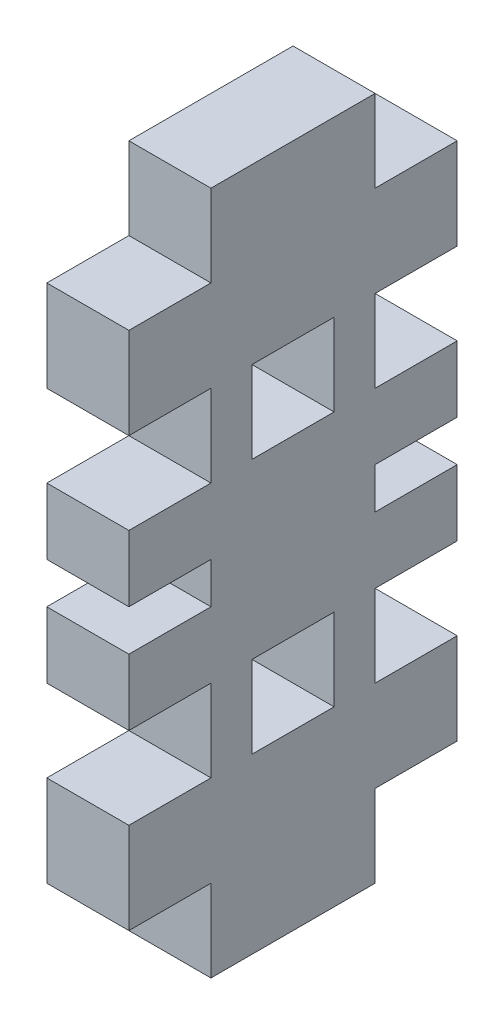
SolidWorks part; units mm, degrees
ref_plane "Front Plane" through (0, 0, 0) normal (0, 0, 1) x (1, 0, 0)
ref_plane "Top Plane" through (0, 0, 0) normal (0, 1, 0) x (1, 0, 0)
ref_plane "Right Plane" through (0, 0, 0) normal (1, 0, 0) x (0, 0, -1)
sketch "Sketch1" plane through (0, 0, 0) normal (0, 0, 1) x (1, 0, 0)
  line L0 (-125, 0) -> (125, 0) construction
  circle A0 centre (-125, 0) radius 4
  circle A1 centre (125, 0) radius 4
  circle A2 centre (-125, 0) radius 8
  circle A3 centre (125, 0) radius 8
  dimension "D1" = 8
  dimension "D3" = 16
  dimension "D2" = 250
extrude "Boss-Extrude1" add sketch "Sketch1" along normal blind 9
sketch "Sketch2" plane through (0, 0, 0) normal (0, 0, 1) x (1, 0, 0)
  line L0 (-125, -25) -> (125, -25) construction
  line L1 (0, -25) -> (0, -75) construction
  line L2 (-125, -75) -> (125, -75)
  line L3 (-125, -75) -> (-125, -25) construction
  line L4 (-175, 0) -> (-125, 0) construction
  line L5 (-175, 0) -> (-175, -75) construction
  line L6 (-125, 0) -> (125, 0) construction
  line L7 (-175, -75) -> (-125, -75)
  line L8 (-275, -75) -> (-175, -75) construction
  line L9 (225, -75) -> (125, -75) construction
  circle A0 centre (-125, 0) radius 25
  circle A1 centre (-125, 0) radius 4
  circle A2 centre (-125, 0) radius 4 construction
  circle A3 centre (125, 0) radius 4
  circle A4 centre (125, 0) radius 25
  circle A5 centre (125, 0) radius 4 construction
  circle A9 centre (-75, 0) radius 4
  circle A10 centre (-175, 0) radius 4
  circle A13 centre (-175, 0) radius 25
  circle A14 centre (-75, 0) radius 25
  circle A15 centre (-275, -75) radius 100
  circle A16 centre (225, -75) radius 100
  circle A17 centre (25, 187.5) radius 187.5
  circle A18 centre (-150, 43.3013) radius 25
  circle A19 centre (-100, 43.3013) radius 25
  dimension "D2" = 50
  dimension "D3" = 50
  dimension "D1" = 50
  dimension "D4" = 50
extrude "Boss-Extrude3" add sketch "Sketch2" along normal blind 9 contours A17 A14 A0 A13 A15 L7 L2 A16 A4 | A4 A3 | A14 A9 | A19 A0 A14 | A0 A1 | A18 A13 A0 | A13 A10 region at (-15.9174, -39.5028, 0) region at (106.5555, -15.8096, 0) region at (-193.176, 16.1176, 0) region at (-150, 14.4338, 0) region at (-146.0383, 12.1464, 0) region at (-54.169, 12.4986, 0) region at (-100, 14.4338, 0)
fillet "Fillet1" radius 1 2 edges at (125, -75, 4.5) (-175, -75, 4.5)
sketch "Sketch3" plane through (0, 0, 0) normal (0, 0, 1) x (1, 0, 0)
  line L0 (25, 0) -> (25, -75)
  line L1 (-174.005, -75) -> (124.005, -75) construction
  line L2 (25, -75) -> (150, -75)
  line L3 (150, -75) -> (150, 25)
  line L4 (150, 25) -> (25, 25)
  line L5 (25, 25) -> (25, 0)
  arc A0 (-63.2353, 22.0588) -> (113.2353, 22.0588) centre (25, 187.5) ccw construction
  arc A1 (145, -15) -> (113.2353, 22.0588) centre (125, 0) ccw construction
extrude "Cut-Extrude1" cut sketch "Sketch3" along normal through all
sketch "Sketch4" plane through (0, -75, 0) normal (0, -1, 0) x (1, 0, 0)
  line L0 (25, 9) -> (-63.2353, 9) construction
  line L1 (20.5, 9) -> (29.5, 9)
  line L2 (20.5, 9) -> (20.5, -18)
  line L3 (20.5, -18) -> (29.5, -18)
  line L4 (29.5, 9) -> (29.5, -18)
  line L5 (25, -18) -> (25, 9) construction
  dimension "D1" = 9
  dimension "D2" = 27
extrude "Boss-Extrude4" add sketch "Sketch4" against normal up to vertex (75 mm away) up to point (25, 0, 0)
sketch "Sketch5" plane through (0, 0, -18) normal (0, 0, -1) x (-1, 0, 0)
  line L0 (-125, -75) -> (-20.5, -75)
  line L1 (-20.5, -75) -> (-20.5, 0)
  line L2 (-20.5, 0) -> (-100, 0)
  circle A0 centre (-125, 0) radius 4
  circle A1 centre (-125, 0) radius 25
  circle A2 centre (-225, -75) radius 100
  circle A3 centre (-225, -75) radius 100 construction
  circle A4 centre (-125, 0) radius 25 construction
  circle A5 centre (-125, 0) radius 4 construction
  circle A6 centre (-25, 187.5) radius 187.5
  circle A7 centre (-25, 187.5) radius 187.5 construction
  line M4 (-29.5, -75) -> (-20.5, -75)
  line M5 (-20.5, -75) -> (-20.5, 0)
  line M6 (-20.5, 0) -> (-29.5, 0)
  line M7 (-29.5, 0) -> (-29.5, -75)
extrude "Boss-Extrude5" add sketch "Sketch5" along normal blind 9 contours A2 L0 L2 A1 M7 | A1 A0 | L2 M7 M4 M5 M6 | A6 A1 L2 region at (76.4581, -39.349, -18) region at (25, -37.5, -18) region at (143.4445, 15.8096, -18) region at (83.4345, 5.5048, -18)
sketch "Sketch6" plane through (0, 0, 0) normal (0, 0, -1) x (-1, 0, 0)
  line L0 (-20.5, 0) -> (-20.5, -25) construction
  line L1 (-20.5, 0) -> (-20.5, -75) construction
  line L2 (-20.5, -25) -> (-20.5, -50) construction
  line L3 (-20.5, -75) -> (-20.5, 0) construction
  line L4 (-20.5, -50) -> (-20.5, -75) construction
ref_plane "Plane1" through (0, -25, 0) normal (0, 1, 0) x (1, 0, 0)
ref_plane "Plane2" through (0, -50, 0) normal (0, 1, 0) x (1, 0, 0)
sketch "Sketch7" plane through (0, -25, 0) normal (0, 1, 0) x (1, 0, 0)
  line L0 (56.5, 18) -> (29.5, 18)
  line L1 (29.5, 18) -> (29.5, -9)
  line L2 (20.5, 27) -> (20.5, 0)
  line L3 (20.5, 0) -> (-6.5, 0)
  circle A0 centre (20.5, 0) radius 27
  circle A1 centre (29.5, 18) radius 27
extrude "Boss-Extrude6" add sketch "Sketch7" along normal blind 4.5 and the other way blind 4.5 contours L1 A1 A0 L0 | A0 A1 L0 | A1 A0 L3 | A0 A1 L3 L2 region at (49.8154, -25, -11.0447) region at (37.3919, -25, -4.7267) region at (0.1846, -25, -6.9553) region at (12.6081, -25, -13.2733)
extrude "Boss-Extrude7" add sketch "Sketch7<3>" along normal blind 4.5 and the other way blind 4.5 from surface contours A0 A1 L0 | L1 A1 A0 L0 | A0 A1 L3 L2 | A1 A0 L3 region at (49.8154, -25, -11.0447) region at (37.3919, -25, -4.7267) region at (0.1846, -25, -6.9553) region at (12.6081, -25, -13.2733) starting at plane "Plane2"
sketch "Sketch7<3>" plane through (0, -25, 0) normal (0, 1, 0) x (1, 0, 0) same geometry as "Sketch7"
sketch "Sketch9" plane through (0, 0, 9) normal (0, 0, 1) x (1, 0, 0)
  line L0 (-174.005, -75) -> (29.5, -75) construction
  line L1 (-164.7085, -50) -> (-155.7085, -50)
  line L2 (-164.7085, -50) -> (-164.7085, -57)
  line L3 (-164.7085, -57) -> (-155.7085, -57)
  line L4 (-155.7085, -50) -> (-155.7085, -57)
  line L5 (-164.7085, -66) -> (-155.7085, -66)
  line L6 (-164.7085, -66) -> (-164.7085, -75)
  line L7 (-164.7085, -75) -> (-155.7085, -75)
  line L8 (-155.7085, -66) -> (-155.7085, -75)
  line L9 (-155.7085, -75) -> (-155.7085, -66) construction
  line L10 (-20.8518, -75) -> (-20.8518, -66) construction
  line L11 (-29.8518, -50) -> (-20.8518, -50)
  line L12 (-29.8518, -50) -> (-29.8518, -57)
  line L13 (-29.8518, -57) -> (-20.8518, -57)
  line L14 (-20.8518, -50) -> (-20.8518, -57)
  line L15 (-29.8518, -66) -> (-20.8518, -66)
  line L16 (-29.8518, -66) -> (-29.8518, -75)
  line L17 (-29.8518, -75) -> (-20.8518, -75)
  line L18 (-20.8518, -66) -> (-20.8518, -75)
  line L19 (125, -75) -> (29.5, -75) construction
  line L20 (105.005, -50) -> (114.005, -50)
  line L21 (105.005, -50) -> (105.005, -57)
  line L22 (105.005, -57) -> (114.005, -57)
  line L23 (114.005, -50) -> (114.005, -57)
  line L24 (105.005, -66) -> (114.005, -66)
  line L25 (105.005, -66) -> (105.005, -75)
  line L26 (105.005, -75) -> (114.005, -75)
  line L27 (114.005, -66) -> (114.005, -75)
extrude "Cut-Extrude2" cut sketch "Sketch9" against normal through all
sketch "Sketch10" plane through (0, 0, 0) normal (0, 1, 0) x (1, 0, 0)
  line L1 (-217.4361, -29.7655) -> (165.8308, -29.7655)
  line L2 (-217.4361, -29.7655) -> (-217.4361, 36.7942)
  line L3 (-217.4361, 36.7942) -> (165.8308, 36.7942)
  line L4 (165.8308, -29.7655) -> (165.8308, 36.7942)
  line L5 (29.5, -9) -> (20.5, -9)
  line L6 (29.5, -9) -> (29.5, 27)
  line L7 (29.5, 27) -> (20.5, 27)
  line L8 (20.5, -9) -> (20.5, 27)
extrude "Cut-Extrude3" cut sketch "Sketch10" against normal through all both and the other way through all
sketch "Sketch12" plane through (20.5, 0, 0) normal (-1, 0, 0) x (0, 0, 1)
  line L0 (-18, -19) -> (9, -19)
  line L1 (-27, -19) -> (-18, -19)
  line L2 (-27, -19) -> (-27, -28)
  line L3 (-27, -28) -> (-18, -28)
  line L4 (-18, -19) -> (-18, -28)
  line L5 (-27, -47) -> (-18, -47)
  line L6 (-27, -47) -> (-27, -56)
  line L7 (-27, -56) -> (-18, -56)
  line L8 (-18, -47) -> (-18, -56)
  line L9 (-27, -75) -> (-27, 0) construction
  line L10 (-18, -75) -> (-18, -56) construction
  line L11 (9, -75) -> (-27, -75) construction
  line L12 (-18, -47) -> (-18, -28) construction
  line L13 (-18, -19) -> (-18, 0) construction
  line L14 (0, 0) -> (-27, 0) construction
  line L15 (9, -75) -> (9, 0.054) construction
  line L16 (9, -19) -> (9, -28)
  line L17 (9, -28) -> (-18, -28)
  line L18 (-18, -47) -> (9, -47)
  line L19 (9, -47) -> (9, -56)
  line L20 (9, -56) -> (-18, -56)
  line L21 (0, -19) -> (0, -56)
  line L22 (-4.5, -56) -> (-4.5, -19)
  line L23 (-9, -19) -> (-9, -56)
  line L24 (-13.5, -19) -> (-13.5, -56)
  line L25 (-18, -66) -> (0, -66) construction
  line L26 (-27, 0) -> (-18, 0)
  line L27 (-27, 0) -> (-27, -9)
  line L28 (-27, -9) -> (-18, -9)
  line L29 (-18, 0) -> (-18, -9)
  line L30 (9, 0.054) -> (0, 0.054)
  line L31 (9, 0.054) -> (9, -9)
  line L32 (9, -9) -> (0, -9)
  line L33 (0, 0.054) -> (0, -9)
  line L34 (-27, -75) -> (-18, -75)
  line L35 (-27, -75) -> (-27, -66)
  line L36 (-27, -66) -> (-18, -66)
  line L37 (-18, -75) -> (-18, -66)
  line L38 (9, -75) -> (0, -75)
  line L39 (9, -75) -> (9, -66)
  line L40 (9, -66) -> (0, -66)
  line L41 (0, -75) -> (0, -66)
  line L42 (-27, -35.25) -> (-18, -35.25)
  line L43 (-27, -35.25) -> (-27, -39.75)
  line L44 (-27, -39.75) -> (-18, -39.75)
  line L45 (-18, -35.25) -> (-18, -39.75)
  line L46 (9, -39.75) -> (0, -39.75)
  line L47 (9, -39.75) -> (9, -35.25)
  line L48 (9, -35.25) -> (0, -35.25)
  line L49 (0, -39.75) -> (0, -35.25)
  line L50 (0, -9) -> (0, -19) construction
  line L51 (0, -66) -> (0, -56) construction
  line L52 (-18, -9) -> (0, -9) construction
  line L53 (-18, -37.5) -> (-9, -37.5) construction
  line L54 (-18, -35.25) -> (0, -35.25) construction
  line L55 (0, -39.75) -> (-18, -39.75) construction
  line L57 (-27, 0) -> (-18, 0)
  line L58 (-27, 0) -> (-27, 5)
  line L59 (-27, 5) -> (-18, 5)
  line L60 (-18, 0) -> (-18, 5)
  line M2 (9, -75) -> (9, 0.054)
  line M6 (-27, 0) -> (-27, -75)
  dimension "D1" = 9
  dimension "D2" = 9
  dimension "D3" = 4.5
  dimension "D4" = 4.5
  dimension "D5" = 9
  dimension "D6" = 4.5
  dimension "D7" = 9
  dimension "D8" = 9
  dimension "D9" = 4.5
  dimension "D10" = 5
extrude "Cut-Extrude4" cut sketch "Sketch12" against normal through all contours L4 L1 L3 M6 | L8 L5 L7 M6 | L18 L21 L20 M2 | L0 L21 L17 M2 | L0 L23 L17 L22 | L0 L24 L17 L23 | L18 L24 L20 L23 | L18 L23 L20 L22 | L27 L26 L29 L28 | L31 L30 L33 L32 | L39 L38 L41 L40 | L35 L34 L37 L36 | L43 L42 L45 L44 | L47 L46 L49 L48 | L58 L57 L60 L59 region at (20.5, -23.5, -22.5) region at (20.5, -23.5, -11.25) region at (20.5, -23.5, -6.75) region at (20.5, -51.5, -11.25) region at (20.5, -23.5, 4.5) region at (20.5, -51.5, -6.75) region at (20.5, -51.5, -22.5) region at (20.5, -51.5, 4.5)
